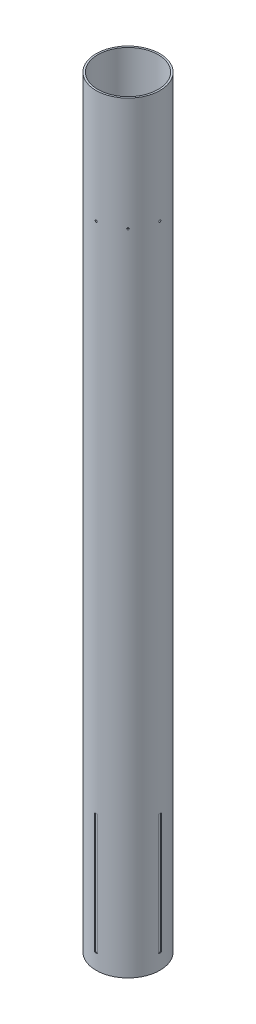
SolidWorks part; units mm, degrees
ref_plane "Front Plane" through (0, 0, 0) normal (0, 0, 1) x (1, 0, 0)
ref_plane "Top Plane" through (0, 0, 0) normal (0, 1, 0) x (1, 0, 0)
ref_plane "Right Plane" through (0, 0, 0) normal (1, 0, 0) x (0, 0, -1)
sketch "Sketch1" plane through (0, 0, 0) normal (0, 1, 0) x (1, 0, 0)
  circle A0 centre (0, 0) radius 53.721
  circle A1 centre (0, 0) radius 50.8
  dimension "D1" = 107.442
  dimension "D2" = 101.6
extrude "Tube Extrusion" add sketch "Sketch1" along normal blind 1282.7
ref_plane "Plane1" through (0, 0, 53.721) normal (0, 0, 1) x (1, 0, 0)
sketch "Sketch2" plane through (0, 0, 53.721) normal (0, 0, 1) x (1, 0, 0)
  line L0 (0, 1282.7) -> (0, 0) construction
  line L3 (53.721, 1282.7) -> (-53.721, 1282.7) construction
  circle A0 centre (0, 1092.2) radius 1.6383
  dimension "D1" = 3.2766
  dimension "D2" = 1092.2
extrude "Engine Block Hole" cut sketch "Sketch2" against normal up to next
pattern_circular "CirPattern1" count 8 over 360 about axis through (0, 1282.7, 0) along (0, -1, 0) of "Engine Block Hole"
sketch "Sketch3" plane through (0, 0, 53.721) normal (0, 0, 1) x (1, 0, 0)
  line L0 (0, 0) -> (0, 25.4) construction
  line L1 (-53.721, 0) -> (53.721, 0) construction
  line L3 (-2.667, 228.6) -> (2.667, 228.6)
  line L4 (-2.667, 228.6) -> (-2.667, 25.4)
  line L5 (-2.667, 25.4) -> (2.667, 25.4)
  line L6 (2.667, 228.6) -> (2.667, 25.4)
  point P8 (0, 25.4)
  dimension "D1" = 25.4
  dimension "D2" = 203.2
  dimension "D3" = 5.334
extrude "Fin Slots" cut sketch "Sketch3" against normal blind 1.27
pattern_circular "CirPattern2" count 4 over 360 about axis through (0, 1282.7, 0) along (0, -1, 0) of "Fin Slots"
